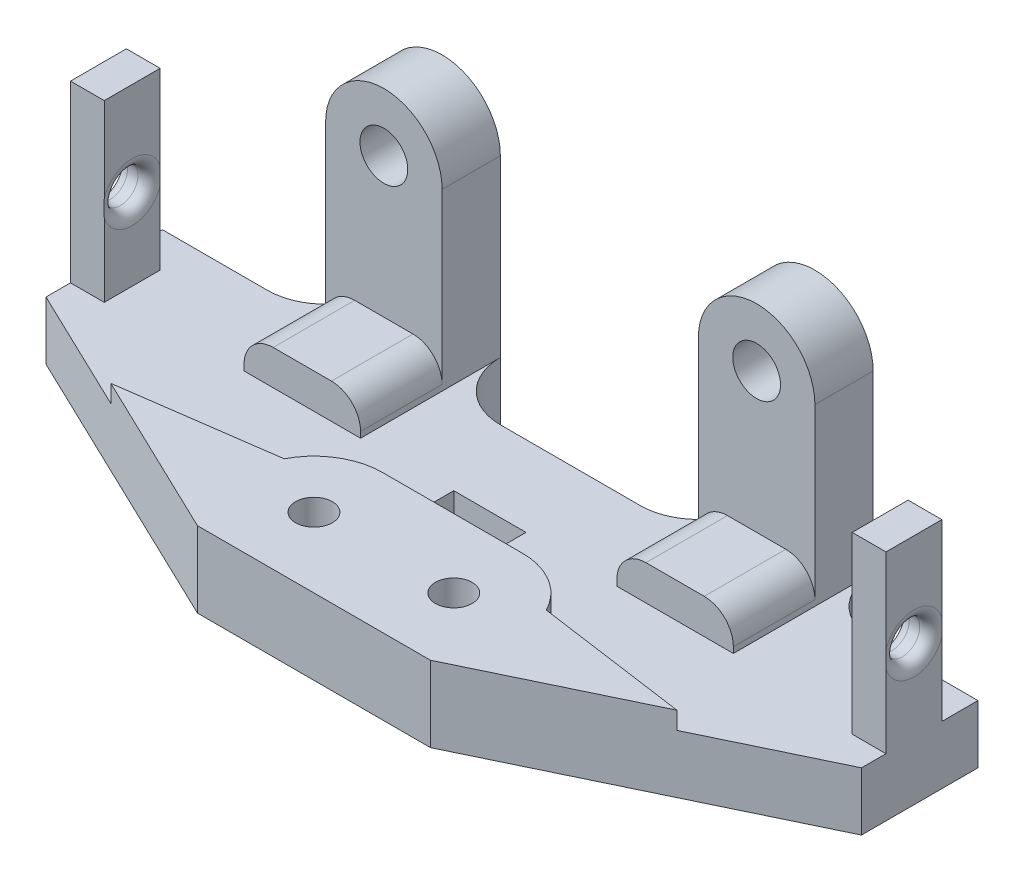
SolidWorks part; units mm, degrees
ref_plane "Front Plane" through (0, 0, 0) normal (0, 0, 1) x (1, 0, 0)
ref_plane "Top Plane" through (0, 0, 0) normal (0, 1, 0) x (1, 0, 0)
ref_plane "Right Plane" through (0, 0, 0) normal (1, 0, 0) x (0, 0, -1)
sketch "Sketch1" plane through (0, 0, 0) normal (0, 1, 0) x (1, 0, 0)
  line L0 (0, 0) -> (20, 0)
  line L1 (10, 0) -> (10, 12) construction
  line L2 (10, 12) -> (-25, 12) construction
  line L3 (0, 0) -> (-25, 12)
  line L4 (-25, 12) -> (-25, 22)
  line L5 (-25, 22) -> (45, 22)
  line L6 (45, 22) -> (45, 12)
  line L7 (45, 12) -> (20, 0)
  dimension "D1" = 35
  dimension "D2" = 20
  dimension "D3" = 12
  dimension "D4" = 70
  dimension "D5" = 10
  dimension "D6" = 10
extrude "Boss-Extrude1" add sketch "Sketch1" along normal blind 5
sketch "Sketch2" plane through (0, 5, 0) normal (0, 1, 0) x (1, 0, 0)
  line L0 (10, 0) -> (10, 22) construction
  line L1 (0, 0) -> (20, 0) construction
  line L2 (45, 22) -> (-25, 22) construction
  circle A0 centre (4, 6) radius 1.575
  circle A1 centre (16, 6) radius 1.575
  dimension "D1" = 3.15
  dimension "D2" = 6
  dimension "D3" = 6
extrude "Cut-Extrude1" cut sketch "Sketch2" against normal blind 3
ref_plane "Plane1" through (0, 0, -6) normal (0, 0, 1) x (1, 0, 0)
sketch "Sketch9" plane through (0, 5, 0) normal (0, 1, 0) x (1, 0, 0)
  line L0 (10, 0) -> (10, 22) construction
  line L1 (0, 0) -> (20, 0) construction
  line L2 (45, 22) -> (-25, 22) construction
  line L3 (10, 11.9) -> (-25, 11.9) construction
  line L4 (-25, 22) -> (-25, 12) construction
  line L5 (-2.75, 6) -> (2.75, 6) construction
  line L7 (6.9, 11.9) -> (13.1, 11.9)
  line L8 (6.9, 11.9) -> (6.9, 15.1)
  line L9 (6.9, 15.1) -> (13.1, 15.1)
  line L10 (13.1, 11.9) -> (13.1, 15.1)
  dimension "D1" = 5.9
  dimension "D2" = 3.1
  dimension "D3" = 3.1
  dimension "D4" = 3.2
sketch "Sketch10" plane through (0, 5, 0) normal (0, 1, 0) x (1, 0, 0)
  line L0 (-25, 22) -> (-25, 12) construction
  line L1 (-25, 18.9) -> (-22.1, 18.9)
  line L2 (-25, 18.9) -> (-25, 14.1)
  line L3 (-25, 14.1) -> (-22.1, 14.1)
  line L4 (-22.1, 18.9) -> (-22.1, 14.1)
  line L5 (45, 22) -> (-25, 22) construction
  line L6 (10, 22) -> (10, 0) construction
  line L7 (0, 0) -> (20, 0) construction
  line L8 (45, 14.1) -> (42.1, 14.1)
  line L9 (42.1, 18.9) -> (42.1, 14.1)
  line L10 (45, 18.9) -> (42.1, 18.9)
  line L11 (45, 18.9) -> (45, 14.1)
  dimension "D1" = 3.1
  dimension "D2" = 4.8
  dimension "D3" = 2.9
extrude "Boss-Extrude2" add sketch "Sketch10" along normal blind 15
extrude "Cut-Extrude4" cut sketch "Sketch9" against normal blind 5
sketch "Sketch11" plane through (-25, 0, 0) normal (-1, 0, 0) x (0, 0, 1)
  circle A0 centre (-16.5, 12) radius 1.5
  dimension "D1" = 3
  dimension "D2" = 7
extrude "Cut-Extrude5" cut sketch "Sketch11" against normal blind 70
fillet "Fillet3" radius 1 1 edges at (-25, 12, -15)
fillet "Fillet4" radius 1 1 edges at (-22.1, 12, -15)
fillet "Fillet6" radius 1 1 edges at (42.1, 12, -18)
fillet "Fillet7" radius 1 1 edges at (45, 12, -15)
sketch "Sketch15" plane through (0, 0, -22) normal (0, 0, -1) x (-1, 0, 0)
  line L0 (-45, 0) -> (25, 0) construction
  line L1 (11, 0) -> (1, 0)
  line L2 (11, 0) -> (11, 20)
  line L4 (1, 0) -> (1, 20)
  arc A0 (1, 20) -> (11, 20) centre (6, 20) cw
  circle A1 centre (6, 20) radius 2.05
  point P1 (6, 25)
  point P6 (6, 0)
  dimension "D4" = 4.1
  dimension "D1" = 25
  dimension "D2" = 19
  dimension "D3" = 10
extrude "Boss-Extrude6" add sketch "Sketch15" along normal blind 5
fillet "Fillet8" radius 5 2 edges at (-11, 2.5, -22) (-1, 2.5, -22)
ref_plane "Plane2" through (10, 0, 0) normal (1, 0, 0) x (0, 0, -1)
sketch "Sketch17" plane through (0, 0, -22) normal (0, 0, 1) x (1, 0, 0)
  line L0 (-1, 20) -> (-1, 5) construction
  line L1 (-11, 5) -> (-1, 5)
  line L2 (-11, 5) -> (-11, 5.5)
  line L3 (-8.5, 8) -> (-3.5, 8)
  line L4 (-1, 5) -> (-1, 5.5)
  arc A0 (-3.5, 8) -> (-1, 5.5) centre (-3.5, 5.5) cw
  arc A1 (-11, 5.5) -> (-8.5, 8) centre (-8.5, 5.5) cw
  point P10 (-1, 8)
  point P13 (-11, 8)
  dimension "D2" = 2.5
  dimension "D1" = 12
extrude "Boss-Extrude7" add sketch "Sketch17" along normal blind 7
sketch "Sketch16" plane through (0, 0, -27) normal (0, 0, -1) x (-1, 0, 0)
  line L0 (1, 0) -> (11, 0) construction
  circle A0 centre (6, 4) radius 2.05
  circle A1 centre (6, 20) radius 2.05 construction
  point P7 (6, 0)
  dimension "D1" = 4.1
  dimension "D2" = 16
extrude "Cut-Extrude6" cut sketch "Sketch16" against normal blind 10
mirror "Mirror1" about plane through (10, 0, 0) normal (1, 0, 0) of "Boss-Extrude7", "Fillet8", "Boss-Extrude6", "Cut-Extrude6"
sketch "Sketch18" plane through (0, 5, 0) normal (0, 1, 0) x (1, 0, 0)
  line L0 (4, 6) -> (-8.7631, 4.2063) construction
  line L1 (-25, 12) -> (0, 0) construction
  line L2 (10, 11.9) -> (10, 0) construction
  line L3 (4, 6) -> (4, 0) construction
  line L4 (0, 0) -> (20, 0) construction
  line L5 (-2.3815, 5.1031) -> (-2.8547, 8.47) construction
  line L6 (-2.8547, 8.47) -> (-14.296, 6.8621) construction
  line L7 (-2.8547, 8.47) -> (4.0172, 9.4358) construction
  line L8 (4, 11.9) -> (16, 11.9)
  line L9 (34.296, 6.8621) -> (20, 0)
  line L10 (21.2481, 8.6958) -> (34.296, 6.8621)
  line L12 (-1.2481, 8.6958) -> (-14.296, 6.8621)
  line L13 (-14.296, 6.8621) -> (0, 0)
  line L14 (0, 0) -> (20, 0)
  arc A0 (-1.2481, 8.6958) -> (4, 11.9) centre (4, 6) cw
  circle A1 centre (4, 6) radius 1.575
  circle A2 centre (16, 6) radius 1.575
  arc A3 (21.2481, 8.6958) -> (16, 11.9) centre (16, 6) ccw
  dimension "D5" = 5.9
  dimension "D6" = 3.15
  dimension "D1" = 82
  dimension "D2" = 3.4
  dimension "D3" = 90
  dimension "D4" = 90
extrude "Boss-Extrude8" add sketch "Sketch18" along normal blind 1.5
